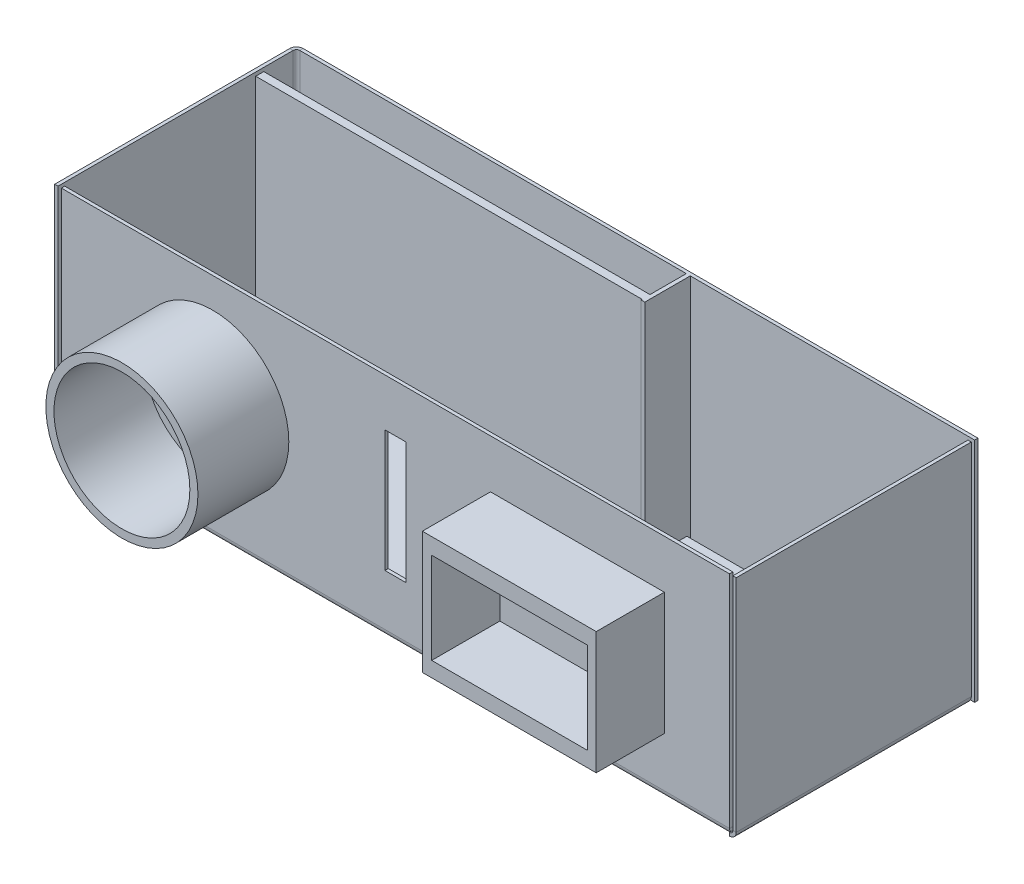
SolidWorks part; units mm, degrees
note: The reader was unsure of these and kept them because the rebuilt part matched: flange length of "Edge-Flange2", "Edge-Flange3", "Edge-Flange5", "Edge-Flange6".
ref_plane "Front Plane" through (0, 0, 0) normal (0, 0, 1) x (1, 0, 0)
ref_plane "Top Plane" through (0, 0, 0) normal (0, 1, 0) x (1, 0, 0)
ref_plane "Right Plane" through (0, 0, 0) normal (1, 0, 0) x (0, 0, -1)
sketch "Sketch1" plane through (0, 0, 0) normal (0, 0, 1) x (1, 0, 0)
  line L1 (-75, 25) -> (75, 25)
  line L2 (-75, 25) -> (-75, -25)
  line L3 (-75, -25) -> (75, -25)
  line L4 (75, 25) -> (75, -25)
  line L5 (-75, 25) -> (75, -25) construction
  line L6 (-75, -25) -> (75, 25) construction
  point P0 (0, 0)
  dimension "D1" = 50
  dimension "D2" = 150
base flange "Base-Flange1" sketch "Sketch1" thickness 0.7366 reverse thickness direction no parameters "D1"=0.7366
edge flange "Edge-Flange2" sketch "Sketch22" flange angle 90 flange length 53.2098 flange position material inside bend radius 0.7366 thickness 0.7366 relief rectangular parameters "D6"=10
sketch "Sketch22" plane through (-75, 0, 0) normal (-1, 0, 0) x (0, -1, 0)
  line L0 (-25, 0) -> (25, 0) construction
  line L1 (-25, 0) -> (25, 0)
  line L2 (-25, 0) -> (-25, 52.4732)
  line L3 (-25, 52.4732) -> (25, 52.4732)
  line L4 (25, 52.4732) -> (25, 0)
bend "EdgeBend5" bend radius 0.7366 bend angle 90 parameters "D5"=1
edge flange "Edge-Flange3" sketch "Sketch25" flange angle 90 flange length 150 flange position material inside bend radius 0.7366 thickness 0.7366 relief none parameters "D6"=10
sketch "Sketch25" plane through (-74.2634, -25, 0) normal (0, -1, 0) x (0, 0, -1)
  line L2 (-52.4732, 0) -> (-52.4732, 149.2634)
  line L3 (-52.4732, 149.2634) -> (-0.7366, 149.2634)
  line L4 (-0.7366, 149.2634) -> (-0.7366, 0)
  line L7 (-0.7366, 0) -> (-52.4732, 0) construction
  line L8 (-0.7366, 0) -> (-52.4732, 0)
bend "EdgeBend6" bend radius 0.7366 bend angle 90 parameters "D5"=2
edge flange "Edge-Flange5" sketch "Sketch32" flange angle 90 flange length 50 flange position material inside bend radius 0.7366 thickness 0.7366 relief rectangular parameters "D6"=10
sketch "Sketch32" plane through (75, -24.2634, 0) normal (-1, 0, 0) x (0, 0, 1)
  line L2 (0.7366, 0) -> (0.7366, 49.2634)
  line L3 (0.7366, 49.2634) -> (52.4732, 49.2634)
  line L4 (52.4732, 49.2634) -> (52.4732, 0)
  line L5 (52.4732, 0) -> (0.7366, 0) construction
  line L6 (52.4732, 0) -> (0.7366, 0)
bend "EdgeBend8" bend radius 0.7366 bend angle 90 parameters "D5"=3
edge flange "Edge-Flange6" sketch "Sketch37" flange angle 90 flange length 50 flange position material inside bend radius 0.7366 thickness 0.7366 relief none parameters "D6"=10
sketch "Sketch37" plane through (0, -24.2634, 52.4732) normal (0, 0, -1) x (-1, 0, 0)
  line L2 (-73.5268, 0) -> (-73.5268, 49.2634)
  line L3 (-73.5268, 49.2634) -> (73.5268, 49.2634)
  line L4 (73.5268, 49.2634) -> (73.5268, 0)
  line L5 (73.5268, 0) -> (-73.5268, 0) construction
  line L6 (73.5268, 0) -> (-73.5268, 0)
bend "EdgeBend9" bend radius 0.7366 bend angle 90 parameters "D5"=4
sketch "Sketch38" plane through (0, 0, 52.4732) normal (0, 0, 1) x (1, 0, 0)
  line L1 (2.3325, -12.2802) -> (-2.3325, -12.2802)
  line L2 (2.3325, -12.2802) -> (2.3325, 14.5309)
  line L3 (2.3325, 14.5309) -> (-2.3325, 14.5309)
  line L4 (-2.3325, -12.2802) -> (-2.3325, 14.5309)
  line L5 (2.3325, -12.2802) -> (-2.3325, 14.5309) construction
  line L6 (2.3325, 14.5309) -> (-2.3325, -12.2802) construction
  point P0 (0, 1.1254)
extrude "Cut-Extrude1" cut sketch "Sketch38" against normal blind 2 contours L2 L3 L4 L1 normal cut yes
sketch "Sketch40" plane through (0, 0, 52.4732) normal (0, 0, 1) x (1, 0, 0)
  circle A0 centre (-40.2045, 1.6599) radius 16.7363
  circle A1 centre (-40.2045, 1.6599) radius 14.9556
extrude "Boss-Extrude4" add sketch "Sketch40" along normal blind 20
sketch "Sketch42" plane through (0, 0, 0) normal (0, 0, 1) x (1, 0, 0)
  line L0 (75, 25) -> (-73.5268, 25) construction
  line L1 (11.5431, -25) -> (12.4081, -25)
  line L2 (11.5431, -25) -> (11.5431, 25)
  line L3 (11.5431, 25) -> (12.4081, 25)
  line L4 (12.4081, -25) -> (12.4081, 25)
  line L5 (11.5431, -25) -> (12.4081, 25) construction
  line L6 (11.5431, 25) -> (12.4081, -25) construction
  point P0 (11.9756, 0)
extrude "Boss-Extrude5" add sketch "Sketch42" along normal blind 10
sketch "Sketch57" plane through (11.5431, 0, 0) normal (-1, 0, 0) x (0, 0, 1)
  line L0 (10, 25) -> (0, 25) construction
  line L1 (9.7672, -31.7229) -> (7.9969, -31.7229)
  line L2 (9.7672, -31.7229) -> (9.7672, 25)
  line L3 (9.7672, 25) -> (7.9969, 25)
  line L4 (7.9969, -31.7229) -> (7.9969, 25)
  line L5 (9.7672, -31.7229) -> (7.9969, 25) construction
  line L6 (9.7672, 25) -> (7.9969, -31.7229) construction
  point P0 (8.8821, -3.3614)
extrude "Boss-Extrude7" add sketch "Sketch57" along normal blind 85
sketch "Sketch60" plane through (0, 0, 52.4732) normal (0, 0, 1) x (1, 0, 0)
  line L1 (59.1871, 14.3278) -> (20.9157, 14.3278)
  line L2 (59.1871, 14.3278) -> (59.1871, -12.5971)
  line L3 (59.1871, -12.5971) -> (20.9157, -12.5971)
  line L4 (20.9157, 14.3278) -> (20.9157, -12.5971)
  line L5 (57.2145, 10.7744) -> (22.9787, 10.7744)
  line L6 (57.2145, 10.7744) -> (57.2145, -9.2727)
  line L7 (57.2145, -9.2727) -> (22.9787, -9.2727)
  line L8 (22.9787, 10.7744) -> (22.9787, -9.2727)
extrude "Boss-Extrude8" add sketch "Sketch60" along normal blind 15
sketch "Sketch61" plane through (0, 0, 51.7366) normal (0, 0, -1) x (-1, 0, 0)
  circle A0 centre (-47.6586, 2.0198) radius 2.0198
extrude "Cut-Extrude3" cut sketch "Sketch61" against normal blind 2 normal cut yes
sketch "Sketch62" plane through (0, 0, 51.7366) normal (0, 0, -1) x (-1, 0, 0)
  circle A0 centre (-63.9481, 1.1472) radius 1.572
extrude "Boss-Extrude9" add sketch "Sketch62" along normal blind 3
sketch "Sketch63" plane through (0, 0, 48.7366) normal (0, 0, -1) x (-1, 0, 0)
  circle A0 centre (-63.6312, 0.9888) radius 7.106
extrude "Boss-Extrude10" add sketch "Sketch63" along normal blind 1.5
sketch "Sketch64" plane through (0, 0, 47.2366) normal (0, 0, -1) x (-1, 0, 0)
  circle A0 centre (-63.7469, 0.7331) radius 6.9805
  circle A1 centre (-63.7469, 0.7331) radius 6.2267
extrude "Boss-Extrude11" add sketch "Sketch64" along normal blind 15
sketch "Bend-Lines1" [suppressed] plane through (0, 0, 0) normal (0, 1, 0) x (1, 0, 0)
sketch "Bounding-Box1" [suppressed] plane through (0, 0, 0) normal (0, 1, 0) x (1, 0, 0)
sheet metal parameters "Sheet-Metal4" thickness 0.7366 parameters "D1"=0.7366
flat pattern "Flat-Pattern4" [suppressed]
sketch "Bend-Lines2" plane through (0, 0, 0) normal (0, 1, 0) x (1, 0, 0)
sketch3d "Bounding-Box2" [suppressed]
  line L0 (-75, -25, 0) -> (75, -25, 0) construction
  line L1 (-75, 25, 0) -> (75, 25, 0) construction
  line L2 (-75, -25, 0) -> (-75, 25, 0) construction
  line L3 (75, -25, 0) -> (75, 25, 0) construction
sheet metal parameters "Sheet-Metal6" thickness 0.7366 parameters "D1"=0.7366
flat pattern "Flat-Pattern4"
sketch "Bend-Lines2" plane through (0, 0, 0) normal (0, 0, 1) x (1, 0, 0)
  line L0 (-74.3946, 25) -> (-74.3946, -25) construction
  line L1 (-74.3946, 25) -> (-74.3946, -25) construction
sketch3d "Bounding-Box2" [suppressed]
  line L0 (-126.999, -25, 0) -> (75, -25, 0) construction
  line L1 (-126.999, 25, 0) -> (75, 25, 0) construction
  line L2 (-126.999, -25, 0) -> (-126.999, 25, 0) construction
  line L3 (75, -25, 0) -> (75, 25, 0) construction
bend of the flat pattern "Flatten-<EdgeBend5>1"
sheet metal parameters "Sheet-Metal7" thickness 0.7366 parameters "D1"=0.7366
flat pattern "Flat-Pattern4"
sketch "Bend-Lines2" plane through (0, 0, 0) normal (0, 0, 1) x (1, 0, 0)
  line L0 (-74.3946, -25) -> (-74.3946, 25) construction
  line L1 (-74.3946, -25) -> (-74.3946, 25) construction
  line L2 (-126.999, -24.3946) -> (-75.2624, -24.3946) construction
  line L3 (-126.999, -24.3946) -> (-75.2624, -24.3946) construction
sketch3d "Bounding-Box2" [suppressed]
  line L0 (-126.999, -173.7892, 0) -> (75, -173.7892, 0) construction
  line L1 (-126.999, 25, 0) -> (75, 25, 0) construction
  line L2 (-126.999, -173.7892, 0) -> (-126.999, 25, 0) construction
  line L3 (75, -173.7892, 0) -> (75, 25, 0) construction
bend of the flat pattern "Flatten-<EdgeBend5>1"
bend of the flat pattern "Flatten-<EdgeBend6>1"
sheet metal parameters "Sheet-Metal9" thickness 0.7366 parameters "D1"=0.7366
flat pattern "Flat-Pattern4"
sketch "Bend-Lines2" plane through (0, 0, 0) normal (0, 0, 1) x (1, 0, 0)
  line L0 (-74.3946, -25) -> (-74.3946, 25) construction
  line L1 (-74.3946, -25) -> (-74.3946, 25) construction
  line L2 (-126.999, -24.3946) -> (-75.2624, -24.3946) construction
  line L3 (-126.999, -24.3946) -> (-75.2624, -24.3946) construction
  line L4 (-126.999, -173.1838) -> (-75.2624, -173.1838) construction
  line L5 (-126.999, -173.1838) -> (-75.2624, -173.1838) construction
sketch3d "Bounding-Box2" [suppressed]
  line L0 (75, 25, 0) -> (75, -222.5783, 0) construction
  line L1 (-126.999, 25, 0) -> (-126.999, -222.5783, 0) construction
  line L2 (75, 25, 0) -> (-126.999, 25, 0) construction
  line L3 (75, -222.5783, 0) -> (-126.999, -222.5783, 0) construction
bend of the flat pattern "Flatten-<EdgeBend5>1"
bend of the flat pattern "Flatten-<EdgeBend6>1"
bend of the flat pattern "Flatten-<EdgeBend8>1"
sheet metal parameters "Sheet-Metal10" thickness 0.7366 parameters "D1"=0.7366
flat pattern "Flat-Pattern4"
sketch "Bend-Lines2" plane through (0, 0, 0) normal (0, 0, 1) x (1, 0, 0)
  line L0 (-74.3946, -25) -> (-74.3946, 25) construction
  line L1 (-74.3946, -25) -> (-74.3946, 25) construction
  line L2 (-126.999, -24.3946) -> (-75.2624, -24.3946) construction
  line L3 (-126.999, -24.3946) -> (-75.2624, -24.3946) construction
  line L4 (-126.999, -173.1838) -> (-75.2624, -173.1838) construction
  line L5 (-126.999, -173.1838) -> (-75.2624, -173.1838) construction
  line L6 (-126.3936, -25.2624) -> (-126.3936, -172.316) construction
  line L7 (-126.3936, -25.2624) -> (-126.3936, -172.316) construction
sketch3d "Bounding-Box2" [suppressed]
  line L0 (-175.7881, -222.5783, 0) -> (75, -222.5783, 0) construction
  line L1 (-175.7881, 25, 0) -> (75, 25, 0) construction
  line L2 (-175.7881, -222.5783, 0) -> (-175.7881, 25, 0) construction
  line L3 (75, -222.5783, 0) -> (75, 25, 0) construction
bend of the flat pattern "Flatten-<EdgeBend5>1"
bend of the flat pattern "Flatten-<EdgeBend6>1"
bend of the flat pattern "Flatten-<EdgeBend8>1"
bend of the flat pattern "Flatten-<EdgeBend9>1"
sheet metal parameters "Sheet-Metal11" thickness 0.7366 parameters "D1"=0.7366
flat pattern "Flat-Pattern4"
sketch "Bend-Lines2" plane through (0, 0, 0) normal (0, 0, 1) x (1, 0, 0)
  line L0 (-74.3946, -25) -> (-74.3946, 25) construction
  line L1 (-74.3946, -25) -> (-74.3946, 25) construction
  line L2 (-126.999, -24.3946) -> (-75.2624, -24.3946) construction
  line L3 (-126.999, -24.3946) -> (-75.2624, -24.3946) construction
  line L4 (-126.999, -173.1838) -> (-75.2624, -173.1838) construction
  line L5 (-126.999, -173.1838) -> (-75.2624, -173.1838) construction
  line L6 (-126.3936, -25.2624) -> (-126.3936, -172.316) construction
  line L7 (-126.3936, -25.2624) -> (-126.3936, -172.316) construction
sketch3d "Bounding-Box2" [suppressed]
  line L0 (-175.7881, -222.5783, 0) -> (75, -222.5783, 0) construction
  line L1 (-175.7881, 25, 0) -> (75, 25, 0) construction
  line L2 (-175.7881, -222.5783, 0) -> (-175.7881, 25, 0) construction
  line L3 (75, -222.5783, 0) -> (75, 25, 0) construction
bend of the flat pattern "Flatten-<EdgeBend5>1"
bend of the flat pattern "Flatten-<EdgeBend6>1"
bend of the flat pattern "Flatten-<EdgeBend8>1"
bend of the flat pattern "Flatten-<EdgeBend9>1"
sheet metal parameters "Sheet-Metal12" thickness 0.7366 parameters "D1"=0.7366
flat pattern "Flat-Pattern4"
sketch "Bend-Lines2" plane through (0, 0, 0) normal (0, 0, 1) x (1, 0, 0)
  line L0 (-74.3946, -25) -> (-74.3946, 25) construction
  line L1 (-74.3946, -25) -> (-74.3946, 25) construction
  line L2 (-126.999, -24.3946) -> (-75.2624, -24.3946) construction
  line L3 (-126.999, -24.3946) -> (-75.2624, -24.3946) construction
  line L4 (-126.999, -173.1838) -> (-75.2624, -173.1838) construction
  line L5 (-126.999, -173.1838) -> (-75.2624, -173.1838) construction
  line L6 (-126.3936, -25.2624) -> (-126.3936, -172.316) construction
  line L7 (-126.3936, -25.2624) -> (-126.3936, -172.316) construction
sketch3d "Bounding-Box2" [suppressed]
  line L0 (-175.7881, -222.5783, 0) -> (75, -222.5783, 0) construction
  line L1 (-175.7881, 25, 0) -> (75, 25, 0) construction
  line L2 (-175.7881, -222.5783, 0) -> (-175.7881, 25, 0) construction
  line L3 (75, -222.5783, 0) -> (75, 25, 0) construction
bend of the flat pattern "Flatten-<EdgeBend5>1"
bend of the flat pattern "Flatten-<EdgeBend6>1"
bend of the flat pattern "Flatten-<EdgeBend8>1"
bend of the flat pattern "Flatten-<EdgeBend9>1"
sheet metal parameters "Sheet-Metal13" thickness 0.7366 parameters "D1"=0.7366
flat pattern "Flat-Pattern4"
sketch "Bend-Lines2" plane through (0, 0, 0) normal (0, 0, 1) x (1, 0, 0)
  line L0 (-74.3946, -25) -> (-74.3946, 25) construction
  line L1 (-74.3946, -25) -> (-74.3946, 25) construction
  line L2 (-126.999, -24.3946) -> (-75.2624, -24.3946) construction
  line L3 (-126.999, -24.3946) -> (-75.2624, -24.3946) construction
  line L4 (-126.999, -173.1838) -> (-75.2624, -173.1838) construction
  line L5 (-126.999, -173.1838) -> (-75.2624, -173.1838) construction
  line L6 (-126.3936, -25.2624) -> (-126.3936, -172.316) construction
  line L7 (-126.3936, -25.2624) -> (-126.3936, -172.316) construction
sketch3d "Bounding-Box2" [suppressed]
  line L0 (-175.7881, -222.5783, 0) -> (75, -222.5783, 0) construction
  line L1 (-175.7881, 25, 0) -> (75, 25, 0) construction
  line L2 (-175.7881, -222.5783, 0) -> (-175.7881, 25, 0) construction
  line L3 (75, -222.5783, 0) -> (75, 25, 0) construction
bend of the flat pattern "Flatten-<EdgeBend5>1"
bend of the flat pattern "Flatten-<EdgeBend6>1"
bend of the flat pattern "Flatten-<EdgeBend8>1"
bend of the flat pattern "Flatten-<EdgeBend9>1"
sheet metal parameters "Sheet-Metal15" thickness 0.7366 parameters "D1"=0.7366
flat pattern "Flat-Pattern4"
sketch "Bend-Lines2" plane through (0, 0, 0) normal (0, 0, 1) x (1, 0, 0)
  line L0 (-74.3946, -25) -> (-74.3946, 25) construction
  line L1 (-74.3946, -25) -> (-74.3946, 25) construction
  line L2 (-126.999, -24.3946) -> (-75.2624, -24.3946) construction
  line L3 (-126.999, -24.3946) -> (-75.2624, -24.3946) construction
  line L4 (-126.999, -173.1838) -> (-75.2624, -173.1838) construction
  line L5 (-126.999, -173.1838) -> (-75.2624, -173.1838) construction
  line L6 (-126.3936, -25.2624) -> (-126.3936, -172.316) construction
  line L7 (-126.3936, -25.2624) -> (-126.3936, -172.316) construction
sketch3d "Bounding-Box2" [suppressed]
  line L0 (-175.7881, -222.5783, 0) -> (75, -222.5783, 0) construction
  line L1 (-175.7881, 25, 0) -> (75, 25, 0) construction
  line L2 (-175.7881, -222.5783, 0) -> (-175.7881, 25, 0) construction
  line L3 (75, -222.5783, 0) -> (75, 25, 0) construction
bend of the flat pattern "Flatten-<EdgeBend5>1"
bend of the flat pattern "Flatten-<EdgeBend6>1"
bend of the flat pattern "Flatten-<EdgeBend8>1"
bend of the flat pattern "Flatten-<EdgeBend9>1"
sheet metal parameters "Sheet-Metal16" thickness 0.7366 parameters "D1"=0.7366
flat pattern "Flat-Pattern4"
sketch "Bend-Lines2" plane through (0, 0, 0) normal (0, 0, 1) x (1, 0, 0)
  line L0 (-74.3946, -25) -> (-74.3946, 25) construction
  line L1 (-74.3946, -25) -> (-74.3946, 25) construction
  line L2 (-126.999, -24.3946) -> (-75.2624, -24.3946) construction
  line L3 (-126.999, -24.3946) -> (-75.2624, -24.3946) construction
  line L4 (-126.999, -173.1838) -> (-75.2624, -173.1838) construction
  line L5 (-126.999, -173.1838) -> (-75.2624, -173.1838) construction
  line L6 (-126.3936, -25.2624) -> (-126.3936, -172.316) construction
  line L7 (-126.3936, -25.2624) -> (-126.3936, -172.316) construction
sketch3d "Bounding-Box2" [suppressed]
  line L0 (-175.7881, -222.5783, 0) -> (75, -222.5783, 0) construction
  line L1 (-175.7881, 25, 0) -> (75, 25, 0) construction
  line L2 (-175.7881, -222.5783, 0) -> (-175.7881, 25, 0) construction
  line L3 (75, -222.5783, 0) -> (75, 25, 0) construction
bend of the flat pattern "Flatten-<EdgeBend5>1"
bend of the flat pattern "Flatten-<EdgeBend6>1"
bend of the flat pattern "Flatten-<EdgeBend8>1"
bend of the flat pattern "Flatten-<EdgeBend9>1"
sheet metal parameters "Sheet-Metal18" thickness 0.7366 parameters "D1"=0.7366
flat pattern "Flat-Pattern4"
sketch "Bend-Lines2" plane through (0, 0, 0) normal (0, 0, 1) x (1, 0, 0)
  line L0 (-74.3946, -25) -> (-74.3946, 25) construction
  line L1 (-74.3946, -25) -> (-74.3946, 25) construction
  line L2 (-126.999, -24.3946) -> (-75.2624, -24.3946) construction
  line L3 (-126.999, -24.3946) -> (-75.2624, -24.3946) construction
  line L4 (-126.999, -173.1838) -> (-75.2624, -173.1838) construction
  line L5 (-126.999, -173.1838) -> (-75.2624, -173.1838) construction
  line L6 (-126.3936, -25.2624) -> (-126.3936, -172.316) construction
  line L7 (-126.3936, -25.2624) -> (-126.3936, -172.316) construction
sketch3d "Bounding-Box2" [suppressed]
  line L0 (-175.7881, -222.5783, 0) -> (75, -222.5783, 0) construction
  line L1 (-175.7881, 25, 0) -> (75, 25, 0) construction
  line L2 (-175.7881, -222.5783, 0) -> (-175.7881, 25, 0) construction
  line L3 (75, -222.5783, 0) -> (75, 25, 0) construction
bend of the flat pattern "Flatten-<EdgeBend5>1"
bend of the flat pattern "Flatten-<EdgeBend6>1"
bend of the flat pattern "Flatten-<EdgeBend8>1"
bend of the flat pattern "Flatten-<EdgeBend9>1"
sheet metal parameters "Sheet-Metal19" thickness 0.7366 parameters "D1"=0.7366
flat pattern "Flat-Pattern4"
sketch "Bend-Lines2" plane through (0, 0, 0) normal (0, 0, 1) x (1, 0, 0)
  line L0 (-74.3946, -25) -> (-74.3946, 25) construction
  line L1 (-74.3946, -25) -> (-74.3946, 25) construction
  line L2 (-126.999, -24.3946) -> (-75.2624, -24.3946) construction
  line L3 (-126.999, -24.3946) -> (-75.2624, -24.3946) construction
  line L4 (-126.999, -173.1838) -> (-75.2624, -173.1838) construction
  line L5 (-126.999, -173.1838) -> (-75.2624, -173.1838) construction
  line L6 (-126.3936, -25.2624) -> (-126.3936, -172.316) construction
  line L7 (-126.3936, -25.2624) -> (-126.3936, -172.316) construction
sketch3d "Bounding-Box2" [suppressed]
  line L0 (-175.7881, -222.5783, 0) -> (75, -222.5783, 0) construction
  line L1 (-175.7881, 25, 0) -> (75, 25, 0) construction
  line L2 (-175.7881, -222.5783, 0) -> (-175.7881, 25, 0) construction
  line L3 (75, -222.5783, 0) -> (75, 25, 0) construction
bend of the flat pattern "Flatten-<EdgeBend5>1"
bend of the flat pattern "Flatten-<EdgeBend6>1"
bend of the flat pattern "Flatten-<EdgeBend8>1"
bend of the flat pattern "Flatten-<EdgeBend9>1"
sheet metal parameters "Sheet-Metal20" thickness 0.7366 parameters "D1"=0.7366
flat pattern "Flat-Pattern4"
sketch "Bend-Lines2" plane through (0, 0, 0) normal (0, 0, 1) x (1, 0, 0)
  line L0 (-74.3946, -25) -> (-74.3946, 25) construction
  line L1 (-74.3946, -25) -> (-74.3946, 25) construction
  line L2 (-126.999, -24.3946) -> (-75.2624, -24.3946) construction
  line L3 (-126.999, -24.3946) -> (-75.2624, -24.3946) construction
  line L4 (-126.999, -173.1838) -> (-75.2624, -173.1838) construction
  line L5 (-126.999, -173.1838) -> (-75.2624, -173.1838) construction
  line L6 (-126.3936, -25.2624) -> (-126.3936, -172.316) construction
  line L7 (-126.3936, -25.2624) -> (-126.3936, -172.316) construction
sketch3d "Bounding-Box2" [suppressed]
  line L0 (-175.7881, -222.5783, 0) -> (75, -222.5783, 0) construction
  line L1 (-175.7881, 25, 0) -> (75, 25, 0) construction
  line L2 (-175.7881, -222.5783, 0) -> (-175.7881, 25, 0) construction
  line L3 (75, -222.5783, 0) -> (75, 25, 0) construction
bend of the flat pattern "Flatten-<EdgeBend5>1"
bend of the flat pattern "Flatten-<EdgeBend6>1"
bend of the flat pattern "Flatten-<EdgeBend8>1"
bend of the flat pattern "Flatten-<EdgeBend9>1"
sheet metal parameters "Sheet-Metal21" thickness 0.7366 parameters "D1"=0.7366
flat pattern "Flat-Pattern4"
sketch "Bend-Lines2" plane through (0, 0, 0) normal (0, 0, 1) x (1, 0, 0)
  line L0 (-74.3946, -25) -> (-74.3946, 25) construction
  line L1 (-74.3946, -25) -> (-74.3946, 25) construction
  line L2 (-126.999, -24.3946) -> (-75.2624, -24.3946) construction
  line L3 (-126.999, -24.3946) -> (-75.2624, -24.3946) construction
  line L4 (-126.999, -173.1838) -> (-75.2624, -173.1838) construction
  line L5 (-126.999, -173.1838) -> (-75.2624, -173.1838) construction
  line L6 (-126.3936, -25.2624) -> (-126.3936, -172.316) construction
  line L7 (-126.3936, -25.2624) -> (-126.3936, -172.316) construction
sketch3d "Bounding-Box2" [suppressed]
  line L0 (-175.7881, -222.5783, 0) -> (75, -222.5783, 0) construction
  line L1 (-175.7881, 25, 0) -> (75, 25, 0) construction
  line L2 (-175.7881, -222.5783, 0) -> (-175.7881, 25, 0) construction
  line L3 (75, -222.5783, 0) -> (75, 25, 0) construction
bend of the flat pattern "Flatten-<EdgeBend5>1"
bend of the flat pattern "Flatten-<EdgeBend6>1"
bend of the flat pattern "Flatten-<EdgeBend8>1"
bend of the flat pattern "Flatten-<EdgeBend9>1"
